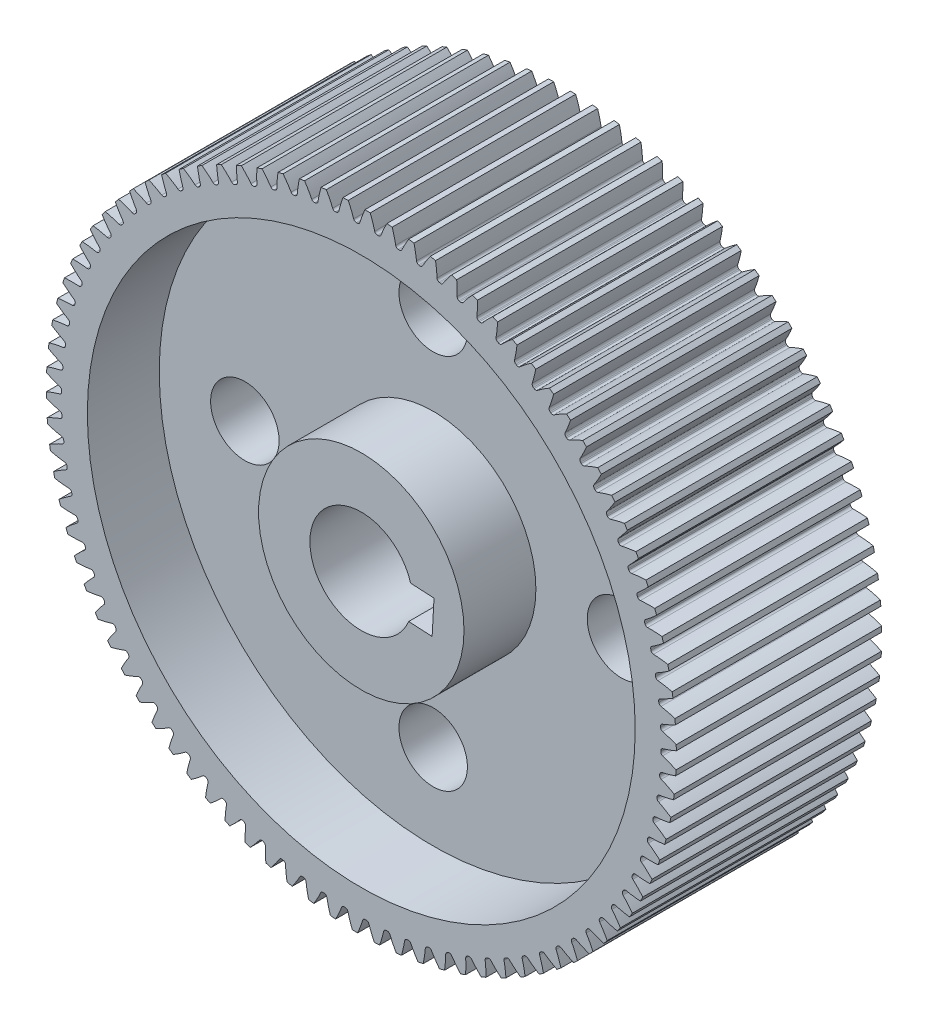
SolidWorks part; units mm, degrees
material "AISI 1045 Steel, cold drawn"
ref_plane "Front" through (0, 0, 0) normal (0, 0, 1) x (1, 0, 0)
ref_plane "Top" through (0, 0, 0) normal (0, 1, 0) x (1, 0, 0)
ref_plane "Right" through (0, 0, 0) normal (1, 0, 0) x (0, 0, -1)
sketch "Sketch3" plane through (0, 0, 0) normal (0, 0, 1) x (1, 0, 0)
  circle A0 centre (0, 0) radius 46
  dimension "od" = 92
extrude "gearBody" add sketch "Sketch3" along normal blind 30
sketch "Sketch2" plane through (0, 0, 0) normal (0, 0, 1) x (1, 0, 0)
  line L0 (0, 0) -> (39.0673, 16.1822) construction
  line L1 (53.0854, -8.5476) -> (0, 0) construction
  line L2 (0, 0) -> (36.3143, 0) construction
  line L3 (44.9999, -0.1016) -> (44.9679, -1.699) construction
  line L5 (44.9839, -0.9003) -> (0, 0) construction
  line L7 (0, 0) -> (42.2862, 0) construction
  arc A0 (42.2777, -0.8487) -> (42.2778, -0.8436) centre (0, 0) ccw construction
  arc A1 (45.999, 0.298) -> (45.9503, -2.1382) centre (0, 0) ccw construction
  arc A2 (44.9999, -0.1016) -> (44.9679, -1.699) centre (0, 0) ccw construction
  arc A3 (43.7388, -0.9516) -> (43.7419, -0.7991) centre (0, 0) ccw
  arc A4 (53.0854, -8.5476) -> (44.0086, -1.3381) centre (38.3886, -17.7323) ccw
  arc A5 (53.0854, -8.5476) -> (53.3849, 6.4168) centre (0, 0) ccw
  arc A6 (53.3849, 6.4168) -> (44.0269, -0.4238) centre (39.0673, 16.1822) cw
  arc A7 (43.7419, -0.7991) -> (44.0269, -0.4238) centre (44.1412, -0.8064) cw
  arc A8 (44.0086, -1.3381) -> (43.7388, -0.9516) centre (44.1381, -0.9603) cw
  point P6 (53.3849, 6.4168)
  point P22 (53.0854, -8.5476)
  dimension "baseDia" = 84.5723
  dimension "od" = 92
  dimension "pd" = 90
  dimension "rd" = 87.4984
  dimension "rFillet" = 0.3993
  dimension "pointX" = 53.3849
  dimension "pointY" = 6.4168
  dimension "CTT" = 1.5974
  dimension "flankCenterAngle" = 22.5
extrude "toothCut" cut sketch "Sketch2" along normal through all
pattern_circular "CirPattern1" count 90 over 360 about axis through (0, 0, 30) along (0, 0, -1) of "toothCut"
ref_axis "toothSpace" through (0, 0, 0) along (0.9998, -0.02, 0)
ref_axis "Axis2" through (45.9307, -2.5249, 0) along (-0.9985, 0.0549, 0)
sketch "hub1Dia" plane through (0, 0, 0) normal (0, 0, -1) x (-1, 0, 0)
  circle A0 centre (0, 0) radius 0.5
  dimension "hub1Dia" = 1
sketch "hub2Dia" plane through (0, 0, 30) normal (0, 0, 1) x (1, 0, 0)
  circle A0 centre (0, 0) radius 0.5
  dimension "hub2dia" = 1
sketch "boreDia" plane through (0, 0, 0) normal (0, 0, 1) x (1, 0, 0)
  circle A0 centre (0, 0) radius 7.5
  dimension "boreDia" = 15
extrude "bore" cut sketch "boreDia" against normal mid plane 25400
sketch "kwy1sketch" plane through (0, 0, 0) normal (0, 0, 1) x (1, 0, 0)
  line L0 (-5.3267, 0.2928) -> (0, 0) construction
  line L1 (10.6214, 1.9199) -> (10.3469, -3.0726)
  line L2 (10.3469, -3.0726) -> (4.1064, -2.7295)
  line L3 (10.6214, 1.9199) -> (4.3808, 2.263)
  line L4 (4.1064, -2.7295) -> (0, 0)
  line L5 (0, 0) -> (4.3808, 2.263)
  line L6 (0, 0) -> (43.7404, -0.8754) construction
  line L7 (10.4842, -0.5763) -> (0, 0) construction
  arc A7 (43.7388, -0.9516) -> (43.7419, -0.7991) centre (0, 0) ccw construction
  point P9 (10.4842, -0.5763)
  point P13 (-0.8885, 0.0488)
  dimension "kwy1width" = 5
  dimension "kwy1depth" = 10.5
  dimension "kwy1angle" = 2
  dimension "kwy1Depth2" = 6.25
extrude "kwy1" cut sketch "kwy1sketch" against normal mid plane 12700
sketch "kwy2sketch" plane through (0, 0, 0) normal (0, 0, 1) x (1, 0, 0)
  line L0 (43.7404, -0.8754) -> (0, 0) construction
  line L1 (0, 0) -> (-2.7459, -2.4597) construction
  line L2 (6.1529, 8.868) -> (9.489, 5.1438)
  line L3 (9.489, 5.1438) -> (4.8337, 0.9736)
  line L4 (6.1529, 8.868) -> (1.4976, 4.6979)
  line L5 (4.8337, 0.9736) -> (0, 0)
  line L6 (0, 0) -> (1.4976, 4.6979)
  arc A2 (43.7388, -0.9516) -> (43.7419, -0.7991) centre (0, 0) ccw construction
  point P10 (7.821, 7.0059)
  dimension "kwy2angle" = 43
  dimension "kwy2Width" = 5
  dimension "kwy2depth" = 10.5
  dimension "kwy2Depth2" = 6.25
sketch "kwy3sketch" plane through (0, 0, 0) normal (0, 0, 1) x (1, 0, 0)
  line L0 (43.7404, -0.8754) -> (0, 0) construction
  line L1 (0, 0) -> (-0.1464, -2.663) construction
  line L2 (-1.9199, 10.6214) -> (3.0726, 10.3469)
  line L3 (3.0726, 10.3469) -> (2.7295, 4.1064)
  line L4 (-1.9199, 10.6214) -> (-2.263, 4.3808)
  line L5 (2.7295, 4.1064) -> (0, 0)
  line L6 (-2.263, 4.3808) -> (0, 0)
  point P10 (0.5763, 10.4842)
  dimension "kwy3angle" = 88
  dimension "kwy3depth" = 10.5
  dimension "kwy3width" = 5
  dimension "kwy3Depth2" = 6.25
sketch "kwy4sketch" plane through (0, 0, 0) normal (0, 0, 1) x (1, 0, 0)
  line L0 (43.7404, -0.8754) -> (0, 0) construction
  line L1 (0, 0) -> (1.3914, -1.5533) construction
  line L2 (-5.1438, 9.489) -> (-8.868, 6.1529)
  line L3 (-8.868, 6.1529) -> (-4.6979, 1.4976)
  line L4 (-4.6979, 1.4976) -> (0, 0)
  line L5 (-0.9736, 4.8337) -> (0, 0)
  line L6 (-5.1438, 9.489) -> (-0.9736, 4.8337)
  point P15 (-7.0059, 7.821)
  dimension "kwy4angle" = 133
  dimension "kwy4depth" = 10.5
  dimension "kwy4width" = 5
  dimension "kwy4Depth2" = 6.25
sketch "kwy5sketch" plane through (0, 0, 0) normal (0, 0, 1) x (1, 0, 0)
  line L0 (43.7404, -0.8754) -> (0, 0) construction
  line L1 (0, 0) -> (1.7883, -0.0983) construction
  line L2 (-10.3469, 3.0726) -> (-10.6214, -1.9199)
  line L3 (-10.6214, -1.9199) -> (-4.3808, -2.263)
  line L4 (-10.3469, 3.0726) -> (-4.1064, 2.7295)
  line L5 (-4.3808, -2.263) -> (0, 0)
  line L6 (-4.1064, 2.7295) -> (0, 0)
  point P10 (-10.4842, 0.5763)
  dimension "kwy5width" = 5
  dimension "kwy5depth" = 10.5
  dimension "kwy5angle" = 178
  dimension "kwy5Depth2" = 6.25
sketch "kwy6sketch" plane through (0, 0, 0) normal (0, 0, 1) x (1, 0, 0)
  line L0 (43.7404, -0.8754) -> (0, 0) construction
  line L1 (0, 0) -> (1.3329, 1.194) construction
  line L2 (-9.489, -5.1438) -> (-6.1529, -8.868)
  line L3 (-6.1529, -8.868) -> (-1.4976, -4.6979)
  line L4 (-9.489, -5.1438) -> (-4.8337, -0.9736)
  line L5 (-1.4976, -4.6979) -> (0, 0)
  line L6 (-4.8337, -0.9736) -> (0, 0)
  point P10 (-7.821, -7.0059)
  dimension "kwy6angle" = 223
  dimension "kwy6width" = 5
  dimension "kwy6depth" = 10.5
  dimension "kwy6Depth2" = 6.25
sketch "kwy7sketch" plane through (0, 0, 0) normal (0, 0, 1) x (1, 0, 0)
  line L0 (43.7404, -0.8754) -> (0, 0) construction
  line L1 (0, 0) -> (0.11, 2.0018) construction
  line L2 (-3.0726, -10.3469) -> (1.9199, -10.6214)
  line L3 (-3.0726, -10.3469) -> (-2.7295, -4.1064)
  line L4 (1.9199, -10.6214) -> (2.263, -4.3808)
  line L5 (-2.7295, -4.1064) -> (0, 0)
  line L6 (2.263, -4.3808) -> (0, 0)
  point P10 (-0.5763, -10.4842)
  dimension "kwy7angle" = 88
  dimension "kwy7width" = 5
  dimension "kwy7depth" = 10.5
  dimension "kwy7angle1" = 268
  dimension "kwy7Depth2" = 6.25
sketch "kwy8sketch" plane through (0, 0, 0) normal (0, 0, 1) x (1, 0, 0)
  line L0 (43.7404, -0.8754) -> (0, 0) construction
  line L1 (0, 0) -> (-1.1885, 1.3267) construction
  line L2 (5.1438, -9.489) -> (8.868, -6.1529)
  line L3 (8.868, -6.1529) -> (4.6979, -1.4976)
  line L4 (5.1438, -9.489) -> (0.9736, -4.8337)
  line L5 (4.6979, -1.4976) -> (0, 0)
  line L6 (0.9736, -4.8337) -> (0, 0)
  point P10 (7.0059, -7.821)
  dimension "kwy8angle" = 313
  dimension "kwy8width" = 5
  dimension "kwy8depth" = 10.5
  dimension "kwy8Depth2" = 6.25
sketch "centerLine" plane through (0, 0, 0) normal (0, 1, 0) x (1, 0, 0)
  line L0 (0, 36.4807) -> (0, -59.6309) construction
ref_plane "CB1plane" through (0, 0, 0) normal (0, 0, -1) x (-1, 0, 0)
sketch "CB1diameter" plane through (0, 0, 0) normal (0, 0, -1) x (-1, 0, 0)
  circle A0 centre (0, 0) radius 0.5
  dimension "CB1diameter" = 1
ref_plane "CB2plane" through (0, 0, 30) normal (0, 0, 1) x (1, 0, 0)
sketch "CB2diameter" plane through (0, 0, 30) normal (0, 0, 1) x (1, 0, 0)
  circle A0 centre (0, 0) radius 0.5
  dimension "CB2diameter" = 1
ref_axis "Axis1" through (0, 0, 50) along (0, 0, -1)
sketch3d "3DSketch1" plane through (0, 0, 0) normal (0, 0, 1) x (1, 0, 0)
sketch "Sketch4" plane through (0, 0, 0) normal (0, 0, -1) x (-1, 0, 0)
  circle A0 centre (0, 0) radius 15
  circle A1 centre (0, 0) radius 40
  dimension "D1" = 80
  dimension "D2" = 30
extrude "Cut-Extrude1" cut sketch "Sketch4" against normal blind 10.5
sketch "Sketch6" plane through (0, 0, 30) normal (0, 0, 1) x (1, 0, 0)
  circle A0 centre (0, 0) radius 15
  circle A1 centre (0, 0) radius 40
  dimension "D1" = 80
  dimension "D2" = 30
extrude "Cut-Extrude2" cut sketch "Sketch6" against normal blind 10.5
sketch "Sketch7" plane through (0, 0, 19.5) normal (0, 0, 1) x (1, 0, 0)
  circle A0 centre (27.5, 0) radius 5
  circle A1 centre (0, 27.5) radius 5
  circle A2 centre (-27.5, 0) radius 5
  circle A3 centre (0, -27.5) radius 5
  dimension "D1" = 10
  dimension "D2" = 10
  dimension "D3" = 10
  dimension "D4" = 10
  dimension "D7" = 27.5
  dimension "D5" = 55
  dimension "D6" = 55
  dimension "D8" = 27.5
extrude "Cut-Extrude3" cut sketch "Sketch7" against normal blind 10.5
